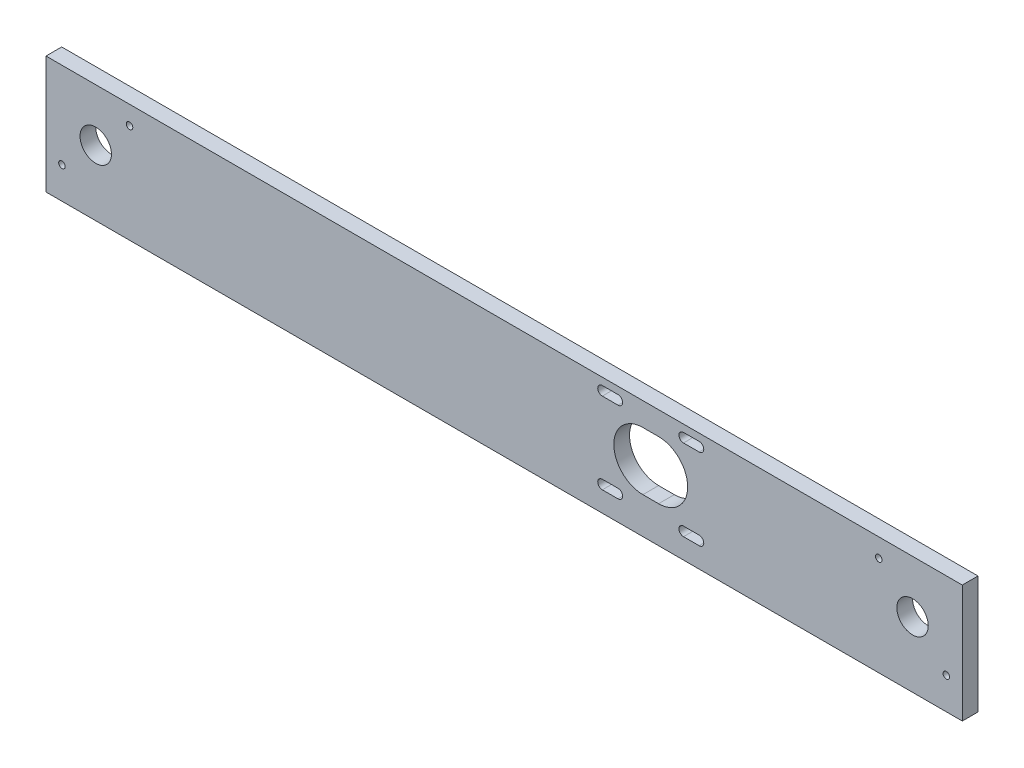
SolidWorks part; units mm, degrees
ref_plane "Alzado" through (0, 0, 0) normal (0, 0, 1) x (1, 0, 0)
ref_plane "Planta" through (0, 0, 0) normal (0, 1, 0) x (1, 0, 0)
ref_plane "Vista lateral" through (0, 0, 0) normal (1, 0, 0) x (0, 0, -1)
sketch "Croquis1" plane through (0, 0, 0) normal (0, 0, 1) x (1, 0, 0)
  line L1 (-350, -45) -> (0, -45)
  line L2 (-350, -45) -> (-350, 0)
  line L3 (-350, 0) -> (0, 0)
  line L4 (0, -45) -> (0, 0)
  dimension "D1" = 350
  dimension "D2" = 45
extrude "Saliente-Extruir1" add sketch "Croquis1" along normal blind 6 contours L3 L4 L1 L2
sketch "Croquis2" plane through (0, 0, 6) normal (0, 0, 1) x (1, 0, 0)
  line L0 (-350, -45) -> (-350, 0) construction
  line L1 (0, -45) -> (0, 0) construction
  line L2 (-350, -45) -> (0, -45) construction
  line L3 (-343.9047, -32.9047) -> (-318.0953, -7.0953) construction
  line L4 (-31.9047, -7.0953) -> (-6.0953, -32.9047) construction
  line L5 (-350, 0) -> (0, 0) construction
  circle A0 centre (-331, -20) radius 6
  circle A1 centre (-19, -20) radius 6
  circle A2 centre (-331, -20) radius 18.25 construction
  circle A4 centre (-318.0953, -7.0953) radius 1.25
  circle A5 centre (-343.9047, -32.9047) radius 1.25
  circle A6 centre (-19, -20) radius 18.25 construction
  circle A7 centre (-31.9047, -7.0953) radius 1.25
  circle A8 centre (-6.0953, -32.9047) radius 1.25
  dimension "D1" = 12
  dimension "D2" = 12
  dimension "D7" = 36.5
  dimension "D9" = 2.5
  dimension "D10" = 2.5
  dimension "D11" = 36.5
  dimension "D13" = 2.5
  dimension "D14" = 2.5
  dimension "D3" = 19
  dimension "D4" = 19
  dimension "D5" = 20
  dimension "D6" = 20
  dimension "D8" = 45
  dimension "D12" = 45
extrude "Cortar-Extruir1" cut sketch "Croquis2" against normal through all
sketch "Croquis3" plane through (0, 0, 6) normal (0, 0, 1) x (1, 0, 0)
  line L3 (-137.5, -4.5) -> (-131.5, -4.5) construction
  line L4 (-137.5, -2.75) -> (-131.5, -2.75)
  line L5 (-137.5, -6.25) -> (-131.5, -6.25)
  line L6 (-122, -20) -> (-116, -20) construction
  line L7 (-122, -8.9) -> (-116, -8.9)
  line L8 (-122, -31.1) -> (-116, -31.1)
  line L9 (-350, 0) -> (0, 0) construction
  line L10 (-137.5, -35.5) -> (-131.5, -35.5) construction
  line L11 (-137.5, -33.75) -> (-131.5, -33.75)
  line L12 (-137.5, -37.25) -> (-131.5, -37.25)
  line L13 (-106.5, -4.5) -> (-100.5, -4.5) construction
  line L14 (-106.5, -2.75) -> (-100.5, -2.75)
  line L15 (-106.5, -6.25) -> (-100.5, -6.25)
  line L16 (-106.5, -35.5) -> (-100.5, -35.5) construction
  line L17 (-106.5, -33.75) -> (-100.5, -33.75)
  line L18 (-106.5, -37.25) -> (-100.5, -37.25)
  arc A5 (-137.5, -2.75) -> (-137.5, -6.25) centre (-137.5, -4.5) ccw
  arc A6 (-131.5, -6.25) -> (-131.5, -2.75) centre (-131.5, -4.5) ccw
  arc A7 (-122, -8.9) -> (-122, -31.1) centre (-122, -20) ccw
  arc A8 (-116, -31.1) -> (-116, -8.9) centre (-116, -20) ccw
  circle A9 centre (-19, -20) radius 6 construction
  arc A11 (-137.5, -33.75) -> (-137.5, -37.25) centre (-137.5, -35.5) ccw
  arc A12 (-131.5, -37.25) -> (-131.5, -33.75) centre (-131.5, -35.5) ccw
  arc A13 (-106.5, -2.75) -> (-106.5, -6.25) centre (-106.5, -4.5) ccw
  arc A14 (-100.5, -6.25) -> (-100.5, -2.75) centre (-100.5, -4.5) ccw
  arc A15 (-106.5, -33.75) -> (-106.5, -37.25) centre (-106.5, -35.5) ccw
  arc A16 (-100.5, -37.25) -> (-100.5, -33.75) centre (-100.5, -35.5) ccw
  point P2 (-119, -20)
  point P12 (-134.5, -4.5)
  point P23 (-134.5, -35.5)
  point P30 (-103.5, -4.5)
  point P37 (-103.5, -35.5)
  dimension "D5" = 1.75
  dimension "D4" = 22.2
  dimension "D9" = 15.5
  dimension "D18" = 1.75
  dimension "D19" = 1.75
  dimension "D20" = 1.75
  dimension "D1" = 100
  dimension "D2" = 20
  dimension "D3" = 6
  dimension "D6" = 15.5
  dimension "D7" = 6
  dimension "D8" = 15.5
  dimension "D10" = 15.5
  dimension "D11" = 15.5
  dimension "D12" = 15.5
  dimension "D13" = 6
  dimension "D14" = 6
  dimension "D15" = 6
  dimension "D16" = 15.5
  dimension "D17" = 15.5
extrude "Cortar-Extruir2" cut sketch "Croquis3" against normal through all
